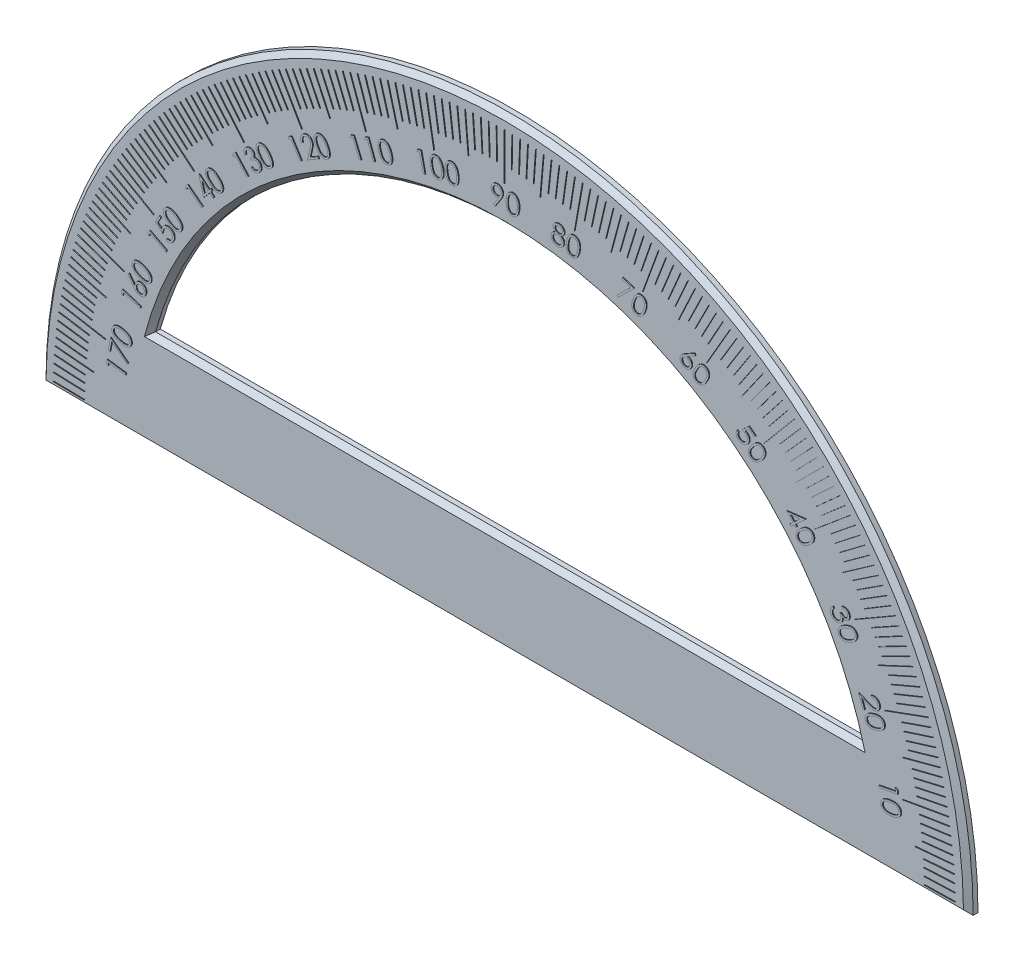
SolidWorks part; units mm, degrees
material "Acrylic (Medium-high impact)"
ref_plane "Front Plane" through (0, 0, 0) normal (0, 0, 1) x (1, 0, 0)
ref_plane "Top Plane" through (0, 0, 0) normal (0, 1, 0) x (1, 0, 0)
ref_plane "Right Plane" through (0, 0, 0) normal (1, 0, 0) x (0, 0, -1)
ref_axis "Axis1" through (0, 0, 1.8002) along (0, 0, -1)
sketch "Sketch1" plane through (0, 0, 0) normal (0, 0, 1) x (1, 0, 0)
  line L0 (-76.2, 0) -> (76.2, 0)
  line L1 (-58.1987, 15.875) -> (58.1987, 15.875)
  arc A0 (-76.2, 0) -> (76.2, 0) centre (0, 0) cw
  arc A1 (-58.1987, 15.875) -> (58.1987, 15.875) centre (0, 0) cw
  point P3 (0, 0)
  dimension "D1" = 76.2
  dimension "D2" = 15.875
extrude "Boss-Extrude1" add sketch "Sketch1" along normal blind 1.5875
chamfer "Chamfer1" distance 0.7937 angle 45 4 edges at (0, 15.875, 1.5875) (0, 60.325, 1.5875) (0, 0, 1.5875) (0, 76.2, 1.5875)
sketch "Sketch3" plane through (0, 0, 0) normal (0, 0, 1) x (1, 0, 0)
  line L0 (76.2, 0) -> (-76.2, 0) construction
  line L1 (-0.7075, 0) -> (0.7075, 0)
  arc A0 (-0.7075, 0) -> (0.7075, 0) centre (0, 0) cw
extrude "Cut-Extrude2" cut sketch "Sketch3" along normal through all
sketch "Sketch4" plane through (0, 0, 1.5875) normal (0, 0, 1) x (1, 0, 0)
  line L0 (74.1321, 0) -> (63.9727, 0) construction
  line L1 (76.2, 0) -> (0.7075, 0) construction
  line L2 (73.01, 12.8736) -> (65.5057, 11.5504) construction
  line L3 (73.8541, 6.4614) -> (67.5283, 5.908) construction
  line L4 (73.2235, 11.5975) -> (68.2061, 10.8028) construction
  line L5 (73.4148, 10.3178) -> (68.3842, 9.6108) construction
  line L6 (73.5836, 9.0349) -> (68.5415, 8.4158) construction
  line L7 (73.7301, 7.7493) -> (68.678, 7.2183) construction
  line L8 (73.9557, 5.1715) -> (68.888, 4.8171) construction
  line L9 (74.0346, 3.88) -> (68.9616, 3.6141) construction
  line L10 (74.0911, 2.5873) -> (69.0142, 2.41) construction
  line L11 (74.125, 1.2939) -> (69.0457, 1.2052) construction
  line L12 (72.7742, 14.1459) -> (67.7875, 13.1766) construction
  line L13 (72.5162, 15.4138) -> (67.5472, 14.3576) construction
  line L14 (72.2361, 16.677) -> (67.2863, 15.5343) construction
  line L15 (71.9341, 17.9352) -> (67.005, 16.7062) construction
  line L16 (71.6101, 19.1879) -> (65.4765, 17.5444) construction
  line L17 (71.2643, 20.4347) -> (66.3811, 19.0345) construction
  line L18 (70.8968, 21.6753) -> (66.0388, 20.1901) construction
  line L19 (70.5078, 22.9094) -> (65.6764, 21.3396) construction
  line L20 (70.0972, 24.1364) -> (65.294, 22.4825) construction
  line L21 (69.6653, 25.3561) -> (62.5048, 22.7499) construction
  line L22 (69.2122, 26.5681) -> (64.4696, 24.7475) construction
  line L23 (68.7379, 27.7719) -> (64.0278, 25.8689) construction
  line L24 (68.2428, 28.9673) -> (63.5666, 26.9824) construction
  line L25 (67.7268, 30.1539) -> (63.086, 28.0877) construction
  line L26 (67.1903, 31.3313) -> (61.4352, 28.6477) construction
  line L27 (66.6332, 32.4992) -> (62.0673, 30.2723) construction
  line L28 (66.0559, 33.6572) -> (61.5296, 31.3509) construction
  line L29 (65.4584, 34.8049) -> (60.9731, 32.4199) construction
  line L30 (64.841, 35.942) -> (60.398, 33.4791) construction
  line L31 (64.2039, 37.0681) -> (57.6048, 33.2581) construction
  line L32 (63.5472, 38.183) -> (59.1928, 35.5666) construction
  line L33 (62.8711, 39.2862) -> (58.563, 36.5942) construction
  line L34 (62.1759, 40.3775) -> (57.9154, 37.6107) construction
  line L35 (61.4617, 41.4565) -> (57.2502, 38.6158) construction
  line L36 (60.7289, 42.5228) -> (55.5272, 38.8806) construction
  line L37 (59.9775, 43.5762) -> (55.8677, 40.5902) construction
  line L38 (59.2078, 44.6163) -> (55.1508, 41.5591) construction
  line L39 (58.4202, 45.6428) -> (54.4171, 42.5153) construction
  line L40 (57.6147, 46.6555) -> (53.6668, 43.4585) construction
  line L41 (56.7917, 47.6539) -> (50.9544, 42.7558) construction
  line L42 (55.9513, 48.6378) -> (52.1174, 45.305) construction
  line L43 (55.094, 49.6068) -> (51.3188, 46.2076) construction
  line L44 (54.2198, 50.5608) -> (50.5045, 47.0962) construction
  line L45 (53.3292, 51.4994) -> (49.6749, 47.9705) construction
  line L46 (52.4222, 52.4222) -> (47.9321, 47.9321) construction
  line L47 (51.4994, 53.3292) -> (47.9705, 49.6749) construction
  line L48 (50.5608, 54.2198) -> (47.0963, 50.5045) construction
  line L49 (49.6068, 55.094) -> (46.2077, 51.3188) construction
  line L50 (48.6378, 55.9513) -> (45.305, 52.1174) construction
  line L51 (47.6539, 56.7917) -> (42.7558, 50.9544) construction
  line L52 (46.6555, 57.6147) -> (43.4585, 53.6668) construction
  line L53 (45.6428, 58.4202) -> (42.5153, 54.4171) construction
  line L54 (44.6163, 59.2078) -> (41.5591, 55.1508) construction
  line L55 (43.5762, 59.9775) -> (40.5902, 55.8677) construction
  line L56 (42.5228, 60.7289) -> (38.8806, 55.5272) construction
  line L57 (41.4565, 61.4617) -> (38.6158, 57.2502) construction
  line L58 (40.3775, 62.1759) -> (37.6107, 57.9154) construction
  line L59 (39.2862, 62.8711) -> (36.5942, 58.563) construction
  line L60 (38.183, 63.5472) -> (35.5666, 59.1928) construction
  line L61 (37.0681, 64.2039) -> (33.2581, 57.6048) construction
  line L62 (35.942, 64.841) -> (33.4791, 60.398) construction
  line L63 (34.8049, 65.4584) -> (32.4199, 60.973) construction
  line L64 (33.6572, 66.0559) -> (31.3509, 61.5296) construction
  line L65 (32.4992, 66.6332) -> (30.2723, 62.0673) construction
  line L66 (31.3313, 67.1903) -> (28.6477, 61.4352) construction
  line L67 (30.1539, 67.7268) -> (28.0877, 63.086) construction
  line L68 (28.9673, 68.2428) -> (26.9824, 63.5666) construction
  line L69 (27.7719, 68.7379) -> (25.8689, 64.0278) construction
  line L70 (26.5681, 69.2122) -> (24.7475, 64.4696) construction
  line L71 (25.3561, 69.6653) -> (22.7499, 62.5048) construction
  line L72 (24.1364, 70.0972) -> (22.4825, 65.294) construction
  line L73 (22.9094, 70.5078) -> (21.3396, 65.6764) construction
  line L74 (21.6753, 70.8968) -> (20.1901, 66.0388) construction
  line L75 (20.4347, 71.2643) -> (19.0345, 66.3811) construction
  line L76 (19.1879, 71.6101) -> (17.5444, 65.4765) construction
  line L77 (17.9352, 71.9341) -> (16.7062, 67.005) construction
  line L78 (16.677, 72.2361) -> (15.5343, 67.2863) construction
  line L79 (15.4138, 72.5162) -> (14.3576, 67.5472) construction
  line L80 (14.1459, 72.7742) -> (13.1766, 67.7875) construction
  line L81 (12.8736, 73.01) -> (11.5504, 65.5057) construction
  line L82 (11.5975, 73.2235) -> (10.8028, 68.2061) construction
  line L83 (10.3178, 73.4148) -> (9.6108, 68.3842) construction
  line L84 (9.0349, 73.5836) -> (8.4158, 68.5415) construction
  line L85 (7.7494, 73.7301) -> (7.2183, 68.678) construction
  line L86 (6.4614, 73.8541) -> (5.908, 67.5283) construction
  line L87 (5.1715, 73.9557) -> (4.8171, 68.888) construction
  line L88 (3.88, 74.0346) -> (3.6141, 68.9616) construction
  line L89 (2.5873, 74.0911) -> (2.41, 69.0142) construction
  line L90 (1.2939, 74.125) -> (1.2052, 69.0457) construction
  line L91 (0, 74.1362) -> (0, 66.5162) construction
  line L92 (-1.2939, 74.125) -> (-1.2052, 69.0457) construction
  line L93 (-2.5873, 74.0911) -> (-2.41, 69.0142) construction
  line L94 (-3.88, 74.0346) -> (-3.6141, 68.9616) construction
  line L95 (-5.1715, 73.9557) -> (-4.8171, 68.888) construction
  line L96 (-6.4614, 73.8541) -> (-5.908, 67.5283) construction
  line L97 (-7.7493, 73.7301) -> (-7.2183, 68.678) construction
  line L98 (-9.0349, 73.5837) -> (-8.4158, 68.5415) construction
  line L99 (-10.3178, 73.4148) -> (-9.6108, 68.3842) construction
  line L100 (-11.5975, 73.2235) -> (-10.8028, 68.2061) construction
  line L101 (-12.8736, 73.01) -> (-11.5504, 65.5057) construction
  line L102 (-14.1459, 72.7742) -> (-13.1766, 67.7875) construction
  line L103 (-15.4138, 72.5162) -> (-14.3576, 67.5472) construction
  line L104 (-16.677, 72.2361) -> (-15.5343, 67.2863) construction
  line L105 (-17.9352, 71.9341) -> (-16.7062, 67.005) construction
  line L106 (-19.1879, 71.6101) -> (-17.5444, 65.4765) construction
  line L107 (-20.4347, 71.2643) -> (-19.0345, 66.3811) construction
  line L108 (-21.6753, 70.8968) -> (-20.1901, 66.0388) construction
  line L109 (-22.9094, 70.5078) -> (-21.3396, 65.6764) construction
  line L110 (-24.1364, 70.0972) -> (-22.4825, 65.294) construction
  line L111 (-25.3561, 69.6653) -> (-22.7499, 62.5048) construction
  line L112 (-26.5681, 69.2122) -> (-24.7475, 64.4696) construction
  line L113 (-27.7719, 68.7379) -> (-25.8689, 64.0278) construction
  line L114 (-28.9673, 68.2428) -> (-26.9824, 63.5666) construction
  line L115 (-30.1539, 67.7268) -> (-28.0877, 63.086) construction
  line L116 (-31.3313, 67.1903) -> (-28.6477, 61.4352) construction
  line L117 (-32.4992, 66.6332) -> (-30.2723, 62.0673) construction
  line L118 (-33.6571, 66.0559) -> (-31.3509, 61.5296) construction
  line L119 (-34.8049, 65.4584) -> (-32.4199, 60.9731) construction
  line L120 (-35.942, 64.841) -> (-33.4791, 60.398) construction
  line L121 (-37.0681, 64.2039) -> (-33.2581, 57.6048) construction
  line L122 (-38.183, 63.5472) -> (-35.5666, 59.1928) construction
  line L123 (-39.2862, 62.8711) -> (-36.5942, 58.563) construction
  line L124 (-40.3775, 62.1759) -> (-37.6107, 57.9154) construction
  line L125 (-41.4565, 61.4617) -> (-38.6158, 57.2502) construction
  line L126 (-42.5228, 60.7289) -> (-38.8806, 55.5272) construction
  line L127 (-43.5762, 59.9775) -> (-40.5902, 55.8677) construction
  line L128 (-44.6163, 59.2078) -> (-41.5591, 55.1508) construction
  line L129 (-45.6428, 58.4202) -> (-42.5153, 54.4171) construction
  line L130 (-46.6555, 57.6147) -> (-43.4585, 53.6668) construction
  line L131 (-47.6539, 56.7917) -> (-42.7558, 50.9544) construction
  line L132 (-48.6378, 55.9513) -> (-45.305, 52.1174) construction
  line L133 (-49.6068, 55.094) -> (-46.2076, 51.3188) construction
  line L134 (-50.5608, 54.2198) -> (-47.0962, 50.5045) construction
  line L135 (-51.4994, 53.3292) -> (-47.9705, 49.6749) construction
  line L136 (-52.4222, 52.4222) -> (-47.9321, 47.9321) construction
  line L137 (-53.3292, 51.4994) -> (-49.6749, 47.9705) construction
  line L138 (-54.2198, 50.5608) -> (-50.5045, 47.0963) construction
  line L139 (-55.094, 49.6068) -> (-51.3188, 46.2077) construction
  line L140 (-55.9513, 48.6378) -> (-52.1174, 45.305) construction
  line L141 (-56.7917, 47.6539) -> (-50.9544, 42.7558) construction
  line L142 (-57.6147, 46.6555) -> (-53.6668, 43.4585) construction
  line L143 (-58.4202, 45.6428) -> (-54.4171, 42.5153) construction
  line L144 (-59.2078, 44.6163) -> (-55.1508, 41.5591) construction
  line L145 (-59.9775, 43.5762) -> (-55.8677, 40.5902) construction
  line L146 (-60.7289, 42.5228) -> (-55.5272, 38.8806) construction
  line L147 (-61.4617, 41.4565) -> (-57.2502, 38.6158) construction
  line L148 (-62.1759, 40.3775) -> (-57.9154, 37.6107) construction
  line L149 (-62.8711, 39.2862) -> (-58.563, 36.5942) construction
  line L150 (-63.5472, 38.183) -> (-59.1928, 35.5666) construction
  line L151 (-64.2039, 37.0681) -> (-57.6048, 33.2581) construction
  line L152 (-64.841, 35.942) -> (-60.398, 33.4791) construction
  line L153 (-65.4584, 34.8049) -> (-60.973, 32.42) construction
  line L154 (-66.0559, 33.6572) -> (-61.5296, 31.3509) construction
  line L155 (-66.6332, 32.4992) -> (-62.0673, 30.2723) construction
  line L156 (-67.1903, 31.3313) -> (-61.4352, 28.6477) construction
  line L157 (-67.7268, 30.1539) -> (-63.086, 28.0877) construction
  line L158 (-68.2428, 28.9673) -> (-63.5666, 26.9824) construction
  line L159 (-68.7379, 27.7719) -> (-64.0278, 25.8689) construction
  line L160 (-69.2121, 26.5681) -> (-64.4696, 24.7476) construction
  line L161 (-69.6653, 25.3561) -> (-62.5048, 22.7499) construction
  line L162 (-70.0972, 24.1364) -> (-65.294, 22.4825) construction
  line L163 (-70.5078, 22.9094) -> (-65.6764, 21.3396) construction
  line L164 (-70.8968, 21.6753) -> (-66.0388, 20.1901) construction
  line L165 (-71.2643, 20.4347) -> (-66.3811, 19.0345) construction
  line L166 (-71.6101, 19.1879) -> (-65.4765, 17.5444) construction
  line L167 (-71.9341, 17.9352) -> (-67.005, 16.7062) construction
  line L168 (-72.2361, 16.677) -> (-67.2863, 15.5343) construction
  line L169 (-72.5162, 15.4138) -> (-67.5472, 14.3576) construction
  line L170 (-72.7742, 14.1459) -> (-67.7875, 13.1766) construction
  line L171 (-73.01, 12.8736) -> (-65.5057, 11.5504) construction
  line L172 (-73.2235, 11.5975) -> (-68.2061, 10.8028) construction
  line L173 (-73.4148, 10.3178) -> (-68.3842, 9.6108) construction
  line L174 (-73.5836, 9.0349) -> (-68.5415, 8.4158) construction
  line L175 (-73.7301, 7.7494) -> (-68.678, 7.2183) construction
  line L176 (-73.8541, 6.4614) -> (-67.5283, 5.908) construction
  line L177 (-73.9557, 5.1715) -> (-68.888, 4.8171) construction
  line L178 (-74.0346, 3.88) -> (-68.9616, 3.6141) construction
  line L179 (-74.0911, 2.5873) -> (-69.0142, 2.41) construction
  line L180 (-74.125, 1.2939) -> (-69.0457, 1.2052) construction
  line L181 (-74.1362, 0) -> (-66.5162, 0) construction
  arc A0 (62.7028, 0.6601) -> (-62.7028, 0.6601) centre (0, 0) ccw construction
  arc A1 (66.5126, 0.7002) -> (-66.5126, 0.7002) centre (0, 0) ccw construction
  arc A2 (74.1321, 0.7804) -> (-74.1321, 0.7804) centre (0, 0) ccw
  arc A3 (74.1321, 0.7804) -> (-74.1321, 0.7804) centre (0, 0) ccw construction
  arc A4 (67.7825, 0.7135) -> (-67.7825, 0.7135) centre (0, 0) ccw construction
  arc A5 (69.0524, 0.7269) -> (-69.0524, 0.7269) centre (0, 0) ccw construction
  text T0 "  170   160   150   140   130   120   110   100    90    80     70     60     50     40      30     20     10      "
  dimension "D7" = 4
  dimension "D5" = 10
  dimension "D6" = 5
  dimension "D8" = 3
  dimension "D9" = 2
  dimension "D10" = 1
  dimension "D11" = 2
  dimension "D13" = 3.81
  dimension "D1" = 1.27
  dimension "D2" = 7.62
  dimension "D3" = 6.35
  dimension "D4" = 5.08
  dimension "D12" = 18
sketch "Sketch6" plane through (0, 0, 1.5875) normal (0, 0, 1) x (1, 0, 0)
  line L3 (74.125, 1.2939) -> (69.0457, 1.2052)
  line L4 (74.0911, 2.5873) -> (69.0142, 2.41)
  line L5 (74.0346, 3.88) -> (68.9616, 3.6141)
  line L6 (73.9557, 5.1715) -> (68.888, 4.8171)
  line L7 (73.8541, 6.4614) -> (67.5283, 5.908)
  line L8 (73.7301, 7.7493) -> (68.678, 7.2183)
  line L9 (73.5836, 9.0349) -> (68.5415, 8.4158)
  line L10 (73.4148, 10.3178) -> (68.3842, 9.6108)
  line L11 (73.2235, 11.5975) -> (68.2061, 10.8028)
  line L12 (73.01, 12.8736) -> (65.5057, 11.5504)
sketch "Sketch7" plane through (0, 0, 1.5875) normal (0, 0, 1) x (1, 0, 0)
  line L0 (69.0457, 1.2052) -> (74.125, 1.2939)
extrude "Extrude-Thin1" add sketch "Sketch7" along normal blind 0.127 thin thin type mid plane wall 0.0254
pattern_circular "CirPattern2" count 179 over 178 about axis through (0, 0, 1.8002) along (0, 0, -1) skipping 4, 9, 14, 19, 24, 29, 34, 39, 44, 49, 54, 59, 64, 69, 74, 79, 84, 89, 94, 99, 104, 109, 114, 119, 124, 129, 134, 139, 144, 149, 154, 159, 164, 169, 174 of "Extrude-Thin1" reverse direction yes
sketch "Sketch8" plane through (0, 0, 1.5875) normal (0, 0, 1) x (1, 0, 0)
  line L0 (67.5283, 5.908) -> (73.8541, 6.4614)
extrude "Extrude-Thin2" add sketch "Sketch8" along normal blind 0.127 thin thin type mid plane wall 0.0254
pattern_circular "CirPattern3" count 18 over 170 about axis through (0, 0, 1.8002) along (0, 0, -1) of "Extrude-Thin2" reverse direction yes
sketch "Sketch9" plane through (0, 0, 1.5875) normal (0, 0, 1) x (1, 0, 0)
  line L0 (65.5057, 11.5504) -> (73.01, 12.8736)
extrude "Extrude-Thin3" add sketch "Sketch9" along normal blind 0.127 thin thin type mid plane wall 0.0254
pattern_circular "CirPattern4" count 17 over 160 about axis through (0, 0, 1.8002) along (0, 0, -1) of "Extrude-Thin3" reverse direction yes
extrude "Boss-Extrude2" add sketch "Sketch4" along normal blind 0.127
